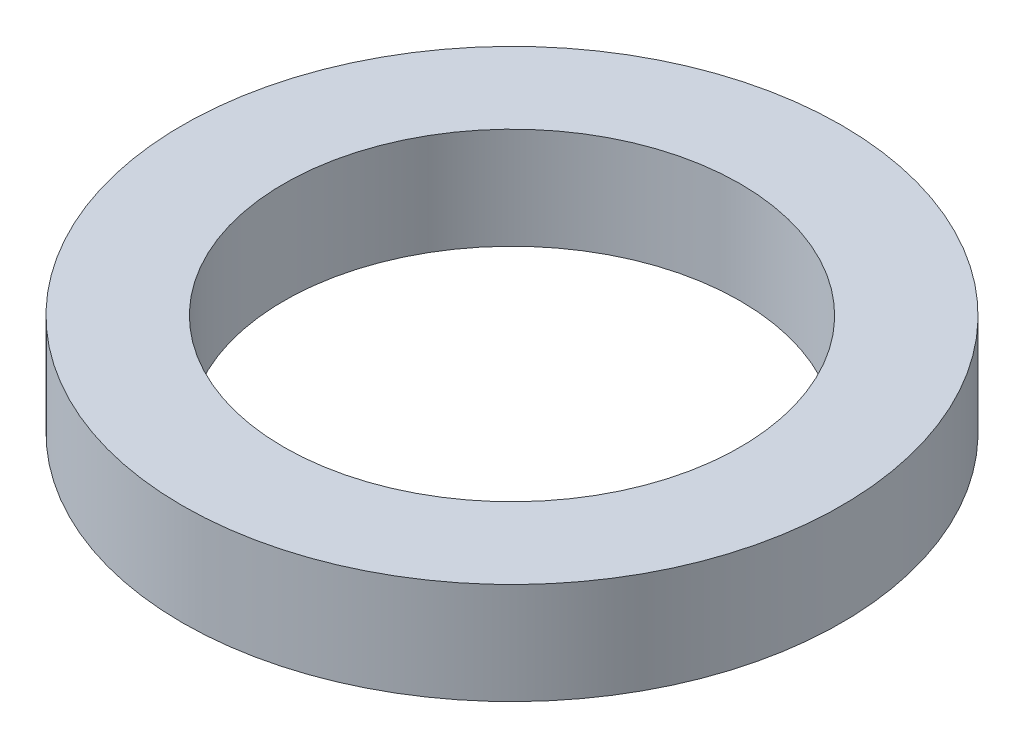
SolidWorks part; units mm, degrees
ref_plane "Front Plane" through (0, 0, 0) normal (0, 0, 1) x (1, 0, 0)
ref_plane "Top Plane" through (0, 0, 0) normal (0, 1, 0) x (1, 0, 0)
ref_plane "Right Plane" through (0, 0, 0) normal (1, 0, 0) x (0, 0, -1)
sketch "Sketch1" plane through (0, 0, 0) normal (0, 1, 0) x (1, 0, 0)
  circle A0 centre (0, 0) radius 32.5
  dimension "FLANGE_OD" = 65
extrude "Boss-Extrude1" add sketch "Sketch1" along normal blind 10
sketch "Sketch2" plane through (0, 0, 0) normal (0, 1, 0) x (1, 0, 0)
  circle A0 centre (0, 0) radius 22.5
  dimension "BORE_D" = 45
extrude "Cut-Extrude1" cut sketch "Sketch2" along normal through all
sketch "Sketch3" plane through (0, 10, 0) normal (0, 1, 0) x (1, 0, 0)
  circle A0 centre (0, 0) radius 13.2171 construction
  circle A1 centre (-13.2171, 0) radius 1.7425
  dimension "BOLT_D" = 3.4851
  dimension "BOLT_PCD" = 26.4343
extrude "Cut-Extrude2" cut sketch "Sketch3" against normal blind 7.7991 rebuild error yes
pattern_circular "CirPattern1" count 3 over 360 rebuild error yes
